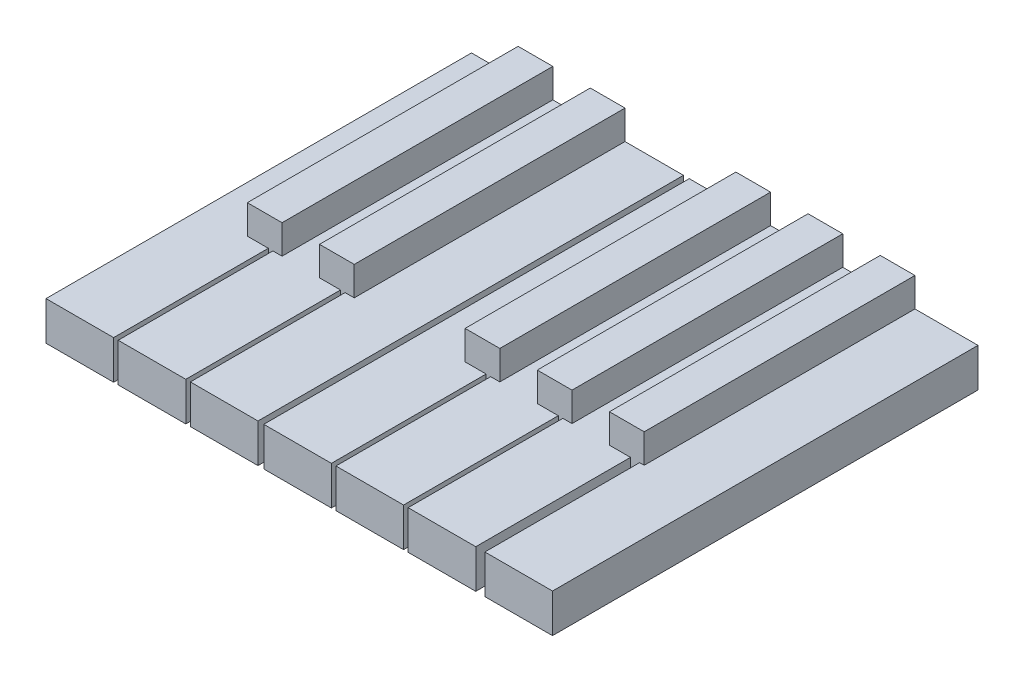
SolidWorks part; units mm, degrees
ref_plane "Front Plane" through (0, 0, 0) normal (0, 0, 1) x (1, 0, 0)
ref_plane "Top Plane" through (0, 0, 0) normal (0, 1, 0) x (1, 0, 0)
ref_plane "Right Plane" through (0, 0, 0) normal (1, 0, 0) x (0, 0, -1)
sketch "Sketch1" plane through (0, 0, 0) normal (0, 1, 0) x (1, 0, 0)
  line L0 (0, 0) -> (145.6, 0) construction
  line L2 (15.3, 0) -> (26.7, 0)
  line L3 (15.3, 0) -> (15.3, -88.9)
  line L4 (15.3, -88.9) -> (26.7, -88.9)
  line L5 (26.7, 0) -> (26.7, -88.9)
  line L6 (39, 0) -> (50.4, 0)
  line L7 (39, 0) -> (39, -88.9)
  line L8 (39, -88.9) -> (50.4, -88.9)
  line L9 (50.4, 0) -> (50.4, -88.9)
  line L10 (86.8, 0) -> (98.2, 0)
  line L11 (86.8, 0) -> (86.8, -88.9)
  line L12 (86.8, -88.9) -> (98.2, -88.9)
  line L13 (98.2, 0) -> (98.2, -88.9)
  line L14 (110.5, 0) -> (121.9, 0)
  line L15 (110.5, 0) -> (110.5, -88.9)
  line L16 (110.5, -88.9) -> (121.9, -88.9)
  line L17 (121.9, 0) -> (121.9, -88.9)
  line L18 (134.2, 0) -> (145.6, 0)
  line L19 (134.2, 0) -> (134.2, -88.9)
  line L20 (134.2, -88.9) -> (145.6, -88.9)
  line L21 (145.6, 0) -> (145.6, -88.9)
  line L22 (0, 0) -> (22.2, 0)
  line L23 (0, 0) -> (0, -139.7)
  line L24 (0, -139.7) -> (22.2, -139.7)
  line L25 (22.2, 0) -> (22.2, -139.7)
  line L26 (23.7, 0) -> (45.9, 0)
  line L27 (23.7, 0) -> (23.7, -139.7)
  line L28 (23.7, -139.7) -> (45.9, -139.7)
  line L29 (45.9, 0) -> (45.9, -139.7)
  line L30 (47.4, 0) -> (69.6, 0)
  line L31 (47.4, 0) -> (47.4, -139.7)
  line L32 (47.4, -139.7) -> (69.6, -139.7)
  line L33 (69.6, 0) -> (69.6, -139.7)
  line L34 (71.5, 0) -> (93.7, 0)
  line L35 (71.5, 0) -> (71.5, -139.7)
  line L36 (71.5, -139.7) -> (93.7, -139.7)
  line L37 (93.7, 0) -> (93.7, -139.7)
  line L38 (95.2, 0) -> (117.4, 0)
  line L39 (95.2, 0) -> (95.2, -139.7)
  line L40 (95.2, -139.7) -> (117.4, -139.7)
  line L41 (117.4, 0) -> (117.4, -139.7)
  line L42 (118.9, 0) -> (141.1, 0)
  line L43 (118.9, 0) -> (118.9, -139.7)
  line L44 (118.9, -139.7) -> (141.1, -139.7)
  line L45 (141.1, 0) -> (141.1, -139.7)
  line L46 (144.1, 0) -> (166.3, 0)
  line L47 (144.1, 0) -> (144.1, -139.7)
  line L48 (144.1, -139.7) -> (166.3, -139.7)
  line L49 (166.3, 0) -> (166.3, -139.7)
  dimension "D1" = 22.2
  dimension "D2" = 11.4
  dimension "D3" = 139.7
  dimension "D4" = 88.9
  dimension "D5" = 6.9
  dimension "D6" = 3
  dimension "D7" = 6.9
  dimension "D8" = 3
  dimension "D9" = 6.9
  dimension "D10" = 3
  dimension "D11" = 1.9
  dimension "D12" = 6.9
  dimension "D13" = 3
  dimension "D14" = 6.9
  dimension "D15" = 3
extrude "Boss-Extrude1" add sketch "Sketch1" along normal blind 12.7 contours L25 L4 L3 L22 L23 L24 | L29 L8 L7 L26 L5 L4 L27 L28 | L33 L30 L9 L8 L31 L32 | L37 L12 L11 L34 L35 L36 | L41 L16 L15 L38 L13 L12 L39 L40 | L45 L20 L19 L42 L17 L16 L43 L44 | L49 L46 L21 L20 L47 L48 region at (9.2139, 0, 76.1125) region at (33.8401, 0, 79.9142) region at (59.4032, 0, 72.2398) region at (80.7139, 0, 76.1125) region at (105.3401, 0, 79.9142) region at (129.0401, 0, 79.9142) region at (155.665, 0, 70.9912)
extrude "Boss-Extrude2" add sketch "Sketch1<4>" along normal blind 22.225 contours L2 L5 L4 L3 | L6 L9 L8 L7 | L10 L13 L12 L11 | L14 L17 L16 L15 | L18 L21 L20 L19
sketch "Sketch1<4>" plane through (0, 0, 0) normal (0, 1, 0) x (1, 0, 0) same geometry as "Sketch1"
